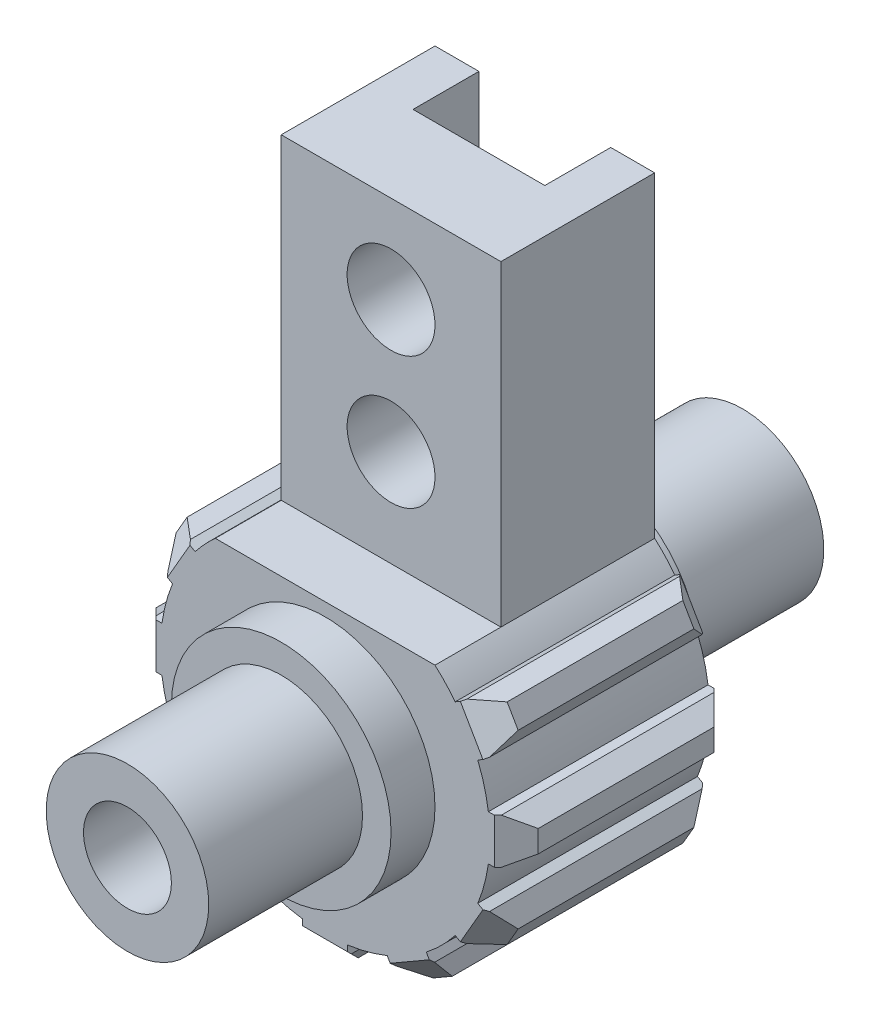
SolidWorks part; units mm, degrees
ref_plane "Front Plane" through (0, 0, 0) normal (0, 0, 1) x (1, 0, 0)
ref_plane "Top Plane" through (0, 0, 0) normal (0, 1, 0) x (1, 0, 0)
ref_plane "Right Plane" through (0, 0, 0) normal (1, 0, 0) x (0, 0, -1)
sketch "Sketch1" plane through (0, 0, 0) normal (0, 0, 1) x (1, 0, 0)
  circle A0 centre (0, 0) radius 7.5
  dimension "D1" = 15
extrude "Boss-Extrude1" add sketch "Sketch1" along normal blind 10
sketch "Sketch2" plane through (0, 0, 10) normal (0, 0, 1) x (1, 0, 0)
  line L0 (0, 0) -> (0, -9.5) construction
  line L1 (-0.5013, -8.7) -> (-1.0275, -7.8603)
  line L2 (0.5013, -8.7) -> (1.0275, -7.8603)
  line L3 (-0.5013, -8.7) -> (0.5013, -8.7)
  line L4 (0, -9.5) -> (-0.5013, -8.7) construction
  line L5 (0, -9.5) -> (0.5013, -8.7) construction
  line L6 (1.0275, -7.4293) -> (1.0275, -7.8603)
  line L7 (-1.0275, -7.4293) -> (-1.0275, -7.8603)
  line L8 (1.0275, -7.8603) -> (1.3275, -7.3816) construction
  line L9 (-1.0275, -7.8603) -> (-1.3275, -7.3816) construction
  line L10 (-2.8248, -6.9477) -> (-3.0403, -7.321)
  line L11 (-3.9158, -7.7851) -> (-3.0403, -7.321)
  line L12 (-4.7842, -7.2838) -> (-3.9158, -7.7851)
  line L13 (-4.7842, -7.2838) -> (-4.82, -6.2935)
  line L14 (-4.6045, -5.9202) -> (-4.82, -6.2935)
  line L15 (-5.9202, -4.6045) -> (-6.2935, -4.82)
  line L16 (-7.2838, -4.7842) -> (-6.2935, -4.82)
  line L17 (-7.7851, -3.9158) -> (-7.2838, -4.7842)
  line L18 (-7.7851, -3.9158) -> (-7.321, -3.0403)
  line L19 (-6.9477, -2.8248) -> (-7.321, -3.0403)
  line L20 (-7.4293, -1.0275) -> (-7.8603, -1.0275)
  line L21 (-8.7, -0.5013) -> (-7.8603, -1.0275)
  line L22 (-8.7, 0.5013) -> (-8.7, -0.5013)
  line L23 (-8.7, 0.5013) -> (-7.8603, 1.0275)
  line L24 (-7.4293, 1.0275) -> (-7.8603, 1.0275)
  line L25 (-6.9477, 2.8248) -> (-7.321, 3.0403)
  line L26 (-7.7851, 3.9158) -> (-7.321, 3.0403)
  line L27 (-7.2838, 4.7842) -> (-7.7851, 3.9158)
  line L28 (-7.2838, 4.7842) -> (-6.2935, 4.82)
  line L29 (-5.9202, 4.6045) -> (-6.2935, 4.82)
  line L30 (-4.6045, 5.9202) -> (-4.82, 6.2935)
  line L31 (-4.7842, 7.2838) -> (-4.82, 6.2935)
  line L32 (-3.9158, 7.7851) -> (-4.7842, 7.2838)
  line L33 (-3.9158, 7.7851) -> (-3.0403, 7.321)
  line L34 (-2.8248, 6.9477) -> (-3.0403, 7.321)
  line L35 (-1.0275, 7.4293) -> (-1.0275, 7.8603)
  line L36 (-0.5013, 8.7) -> (-1.0275, 7.8603)
  line L37 (0.5013, 8.7) -> (-0.5013, 8.7)
  line L38 (0.5013, 8.7) -> (1.0275, 7.8603)
  line L39 (1.0275, 7.4293) -> (1.0275, 7.8603)
  line L40 (2.8248, 6.9477) -> (3.0403, 7.321)
  line L41 (3.9158, 7.7851) -> (3.0403, 7.321)
  line L42 (4.7842, 7.2838) -> (3.9158, 7.7851)
  line L43 (4.7842, 7.2838) -> (4.82, 6.2935)
  line L44 (4.6045, 5.9202) -> (4.82, 6.2935)
  line L45 (5.9202, 4.6045) -> (6.2935, 4.82)
  line L46 (7.2838, 4.7842) -> (6.2935, 4.82)
  line L47 (7.7851, 3.9158) -> (7.2838, 4.7842)
  line L48 (7.7851, 3.9158) -> (7.321, 3.0403)
  line L49 (6.9477, 2.8248) -> (7.321, 3.0403)
  line L50 (7.4293, 1.0275) -> (7.8603, 1.0275)
  line L51 (8.7, 0.5013) -> (7.8603, 1.0275)
  line L52 (8.7, -0.5013) -> (8.7, 0.5013)
  line L53 (8.7, -0.5013) -> (7.8603, -1.0275)
  line L54 (7.4293, -1.0275) -> (7.8603, -1.0275)
  line L55 (6.9477, -2.8248) -> (7.321, -3.0403)
  line L56 (7.7851, -3.9158) -> (7.321, -3.0403)
  line L57 (7.2838, -4.7842) -> (7.7851, -3.9158)
  line L58 (7.2838, -4.7842) -> (6.2935, -4.82)
  line L59 (5.9202, -4.6045) -> (6.2935, -4.82)
  line L60 (4.6045, -5.9202) -> (4.82, -6.2935)
  line L61 (4.7842, -7.2838) -> (4.82, -6.2935)
  line L62 (3.9158, -7.7851) -> (4.7842, -7.2838)
  line L63 (3.9158, -7.7851) -> (3.0403, -7.321)
  line L64 (2.8248, -6.9477) -> (3.0403, -7.321)
  circle A0 centre (0, 0) radius 7.5 construction
  arc A1 (1.0275, -7.4293) -> (1.3275, -7.3816) centre (0, 0) ccw construction
  circle A2 centre (0, 0) radius 7.5
  arc A3 (-1.0275, -7.4293) -> (1.0275, -7.4293) centre (0, 0) ccw
  arc A4 (-1.3275, -7.3816) -> (-1.0275, -7.4293) centre (0, 0) ccw construction
  arc A5 (-4.6045, -5.9202) -> (-2.8248, -6.9477) centre (0, 0) ccw
  arc A6 (-6.9477, -2.8248) -> (-5.9202, -4.6045) centre (0, 0) ccw
  arc A7 (-7.4293, 1.0275) -> (-7.4293, -1.0275) centre (0, 0) ccw
  arc A8 (-5.9202, 4.6045) -> (-6.9477, 2.8248) centre (0, 0) ccw
  arc A9 (-2.8248, 6.9477) -> (-4.6045, 5.9202) centre (0, 0) ccw
  arc A10 (1.0275, 7.4293) -> (-1.0275, 7.4293) centre (0, 0) ccw
  arc A11 (4.6045, 5.9202) -> (2.8248, 6.9477) centre (0, 0) ccw
  arc A12 (6.9477, 2.8248) -> (5.9202, 4.6045) centre (0, 0) ccw
  arc A13 (7.4293, -1.0275) -> (7.4293, 1.0275) centre (0, 0) ccw
  arc A14 (5.9202, -4.6045) -> (6.9477, -2.8248) centre (0, 0) ccw
  arc A15 (2.8248, -6.9477) -> (4.6045, -5.9202) centre (0, 0) ccw
  point P11 (0, -7.5)
  point P120 (0, 0)
  dimension "D1" = 9.5
  dimension "D2" = 2.5
  dimension "D4" = 1.2
  dimension "D5" = 0.3
  dimension "D3" = 0
  dimension "D6" = 12
extrude "Boss-Extrude2" add sketch "Sketch2" against normal up to surface (10 mm away) up to face at (7.5, 0, 0)
sketch "Sketch4" plane through (0, 0, 0) normal (0, 0, -1) x (-1, 0, 0)
  circle A0 centre (0, 0) radius 4
  circle A1 centre (0, 0) radius 2
  dimension "D1" = 8
  dimension "D2" = 4
extrude "Boss-Extrude3" add sketch "Sketch4" along normal blind 2
sketch "Sketch5" plane through (0, 0, -2) normal (0, 0, -1) x (-1, 0, 0)
  circle A0 centre (0, 0) radius 2 construction
  circle A1 centre (0, 0) radius 2
extrude "Cut-Extrude1" cut sketch "Sketch5" against normal through all
sketch "Sketch6" plane through (0, 0, 10) normal (0, 0, 1) x (1, 0, 0)
  line L1 (-5, 20) -> (5, 20)
  line L2 (-5, 20) -> (-5, 0)
  line L3 (-5, 0) -> (5, 0)
  line L4 (5, 20) -> (5, 0)
  point P4 (0, 0)
  dimension "D1" = 10
  dimension "D2" = 20
extrude "Boss-Extrude4" add sketch "Sketch6" against normal up to surface (10 mm away) up to face at (4, 0, 0)
sketch "Sketch7" plane through (0, 0, -2) normal (0, 0, -1) x (-1, 0, 0)
  circle A0 centre (0, 0) radius 2 construction
  circle A1 centre (0, 0) radius 2
extrude "Cut-Extrude2" cut sketch "Sketch7" against normal through all
sketch "Sketch8" plane through (0, 0, 10) normal (0, 0, 1) x (1, 0, 0)
  circle A0 centre (0, 0) radius 2 construction
  circle A1 centre (0, 0) radius 4
  circle A2 centre (0, 0) radius 4
  circle A3 centre (0, 0) radius 2
  dimension "D1" = 0
extrude "Boss-Extrude5" add sketch "Sketch8" along normal blind 2
sketch "Sketch9" plane through (-5, 0, 0) normal (-1, 0, 0) x (0, 0, 1)
  line L0 (0, 20) -> (10, 20) construction
  line L1 (10, 20) -> (7, 20)
  line L2 (10, 20) -> (10, 7.4602)
  line L3 (10, 7.4602) -> (7, 7.4602)
  line L4 (7, 20) -> (7, 7.4602)
  line L5 (10, 20) -> (10, 5.5902) construction
  dimension "D1" = 3
extrude "Cut-Extrude3" cut sketch "Sketch9" against normal blind 10
sketch "Sketch11" plane through (0, 0, 7) normal (0, 0, 1) x (1, 0, 0)
  line L0 (0, 20) -> (0, 7.4602) construction
  line L1 (5, 20) -> (-5, 20) construction
  line L2 (5, 7.4602) -> (-5, 7.4602) construction
  circle A0 centre (0, 16) radius 2
  circle A1 centre (0, 10) radius 2
  dimension "D1" = 4
  dimension "D2" = 4
  dimension "D3" = 6
  dimension "D4" = 4
extrude "Cut-Extrude4" cut sketch "Sketch11" against normal blind 10
sketch "Sketch12" plane through (0, 0, 0) normal (0, 0, -1) x (-1, 0, 0)
  line L0 (0, 20) -> (0, 4) construction
  line L1 (-3, 20) -> (3, 20)
  line L2 (-3, 20) -> (-3, 5)
  line L3 (-3, 5) -> (3, 5)
  line L4 (3, 20) -> (3, 5)
  line L5 (5, 20) -> (-5, 20) construction
  circle A0 centre (0, 0) radius 4 construction
  circle A1 centre (0, 0) radius 4 construction
  point P12 (0, 20)
  dimension "D1" = 6
  dimension "D2" = 15
extrude "Cut-Extrude5" cut sketch "Sketch12" against normal blind 3
chamfer "Chamfer1" distance 1 angle 45 18 edges at (7.5344, 4.35, 0) (8.7, 0, 0) (7.5344, -4.35, 0) (4.35, -7.5344, 0) (0, -8.7, 0) (-4.35, -7.5344, 0) (-7.5344, -4.35, 0) (-8.7, 0, 0) (-7.5344, 4.35, 0) (-8.7, 0, 10) (-7.5344, 4.35, 10) (7.5344, 4.35, 10) (8.7, 0, 10) (7.5344, -4.35, 10) (4.35, -7.5344, 10) (0, -8.7, 10) (-4.35, -7.5344, 10) (-7.5344, -4.35, 10) tangent propagation no
sketch "Sketch14" plane through (0, 0, -2) normal (0, 0, -1) x (-1, 0, 0)
  circle A2 centre (0, 0) radius 2 construction
  circle A3 centre (0, 0) radius 3.7
  circle A4 centre (0, 0) radius 2
extrude "Boss-Extrude6" add sketch "Sketch14" along normal blind 7
sketch "Sketch15" plane through (0, 0, 12) normal (0, 0, 1) x (1, 0, 0)
  circle A2 centre (0, 0) radius 2 construction
  circle A3 centre (0, 0) radius 3.7
  circle A4 centre (0, 0) radius 2
extrude "Boss-Extrude7" add sketch "Sketch15" along normal blind 7
sketch "Sketch16" plane through (0, 0, 10) normal (0, 0, 1) x (1, 0, 0)
  circle A1 centre (0, 0) radius 4 construction
  circle A2 centre (0, 0) radius 5
  circle A3 centre (0, 0) radius 5
  circle A4 centre (0, 0) radius 4
  dimension "D1" = 1
extrude "Boss-Extrude8" add sketch "Sketch16" along normal up to surface (2 mm away) up to face at (3.7, 0, 12)
sketch "Sketch17" plane through (0, 0, 0) normal (0, 0, -1) x (-1, 0, 0)
  circle A2 centre (0, 0) radius 5
  circle A3 centre (0, 0) radius 5
  dimension "D1" = 1
extrude "Boss-Extrude9" add sketch "Sketch17" along normal up to surface (2 mm away) up to face at (-3.7, 0, -2)
sketch "Sketch18" plane through (0, 0, -9) normal (0, 0, -1) x (-1, 0, 0)
  circle A0 centre (0, 0) radius 2 construction
  circle A1 centre (0, 0) radius 2
extrude "Cut-Extrude6" cut sketch "Sketch18" against normal through all
sketch "Sketch20" plane through (0, 0, 7) normal (0, 0, 1) x (1, 0, 0)
  line L1 (-5, 7.4602) -> (5, 7.4602)
  line L2 (-5, 7.4602) -> (-5, 5.5902)
  line L3 (-5, 5.5902) -> (5, 5.5902)
  line L4 (5, 7.4602) -> (5, 5.5902)
extrude "Cut-Extrude7" cut sketch "Sketch20" along normal through all
